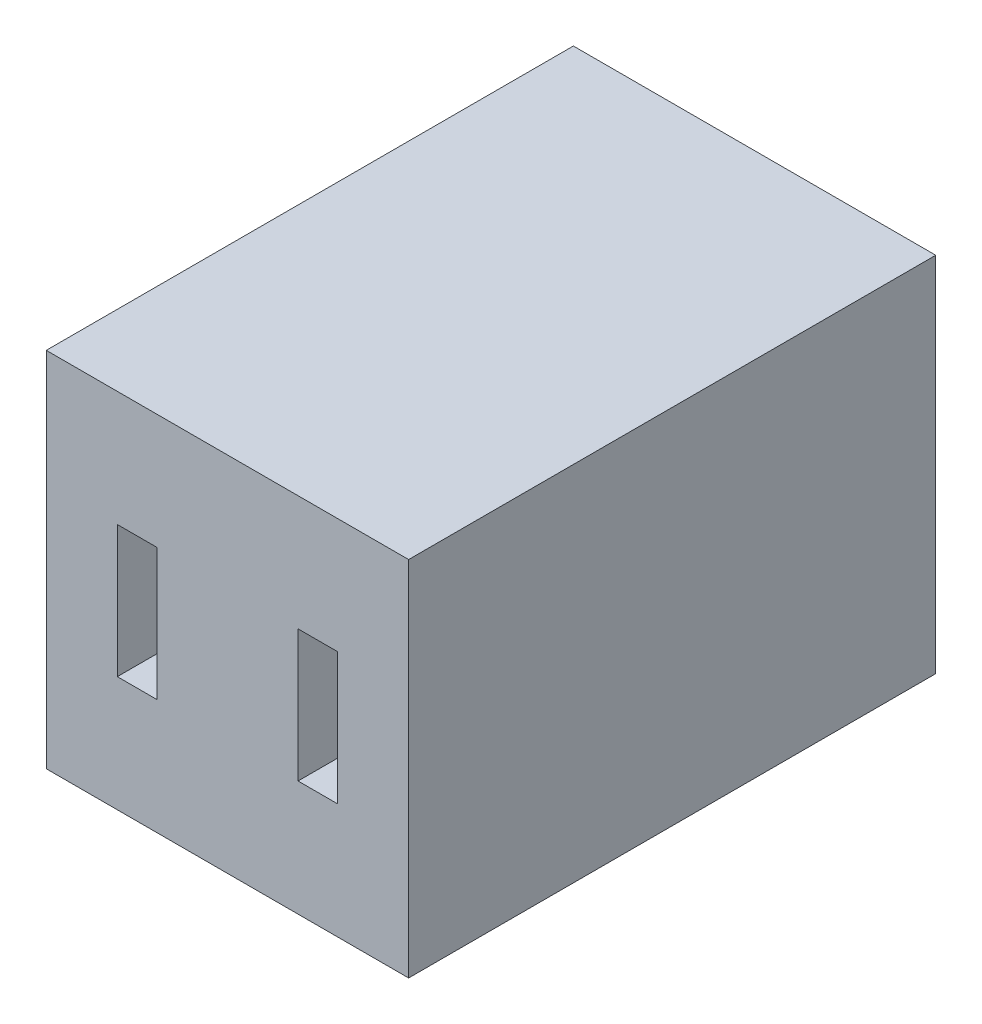
SolidWorks part; units mm, degrees
material "PLA"
ref_plane "Front Plane" through (0, 0, 0) normal (1, 0, 0) x (0, 1, 0)
ref_plane "Top Plane" through (0, 0, 0) normal (0, 0, 1) x (0, 1, 0)
ref_plane "Right Plane" through (0, 0, 0) normal (0, 1, 0) x (-1, 0, 0)
sketch "Sketch1" plane through (0, 0, 0) normal (0, 0, 1) x (0, 1, 0)
  line L1 (-13.75, -13.75) -> (13.75, -13.75)
  line L2 (-13.75, -13.75) -> (-13.75, 13.75)
  line L3 (-13.75, 13.75) -> (13.75, 13.75)
  line L4 (13.75, -13.75) -> (13.75, 13.75)
  line L5 (-13.75, -13.75) -> (13.75, 13.75) construction
  line L6 (-13.75, 13.75) -> (13.75, -13.75) construction
  point P0 (0, 0)
  dimension "D2" = 27.5
extrude "Boss-Extrude1" add sketch "Sketch1" along normal blind 40
sketch "Sketch2" plane through (0, 0, 40) normal (0, 0, 1) x (1, 0, 0)
  line L4 (8.3576, 5) -> (5.3576, 5)
  line L5 (5.3576, 5) -> (5.3576, -5)
  line L6 (5.3576, -5) -> (8.3576, -5)
  line L7 (8.3576, -5) -> (8.3576, 5)
  line L8 (8.3576, 5) -> (5.3576, 5)
  line L9 (5.3576, 5) -> (5.3576, -5)
  line L10 (5.3576, -5) -> (8.3576, -5)
  line L11 (8.3576, -5) -> (8.3576, 5)
  line L12 (-5.3576, -5) -> (-5.3576, 5)
  line L13 (-5.3576, 5) -> (-8.3576, 5)
  line L14 (-8.3576, 5) -> (-8.3576, -5)
  line L15 (-8.3576, -5) -> (-5.3576, -5)
  line L16 (-5.3576, -5) -> (-5.3576, 5)
  line L17 (-5.3576, 5) -> (-8.3576, 5)
  line L18 (-8.3576, 5) -> (-8.3576, -5)
  line L19 (-8.3576, -5) -> (-5.3576, -5)
  dimension "D1" = 0
  dimension "D2" = 0
extrude "Cut-Extrude1" cut sketch "Sketch2" against normal through all
equation "\"ball_diameter\"= 0.75in"
equation "\"wall_thickness\" = 0.25cm"
equation "\"track_length\" = 25cm"
equation "\"axle\" = 5mm"
equation "\"pillar_width\" = 2.75cm"
equation "\"D2@Sketch1\"=\"pillar_width\""
